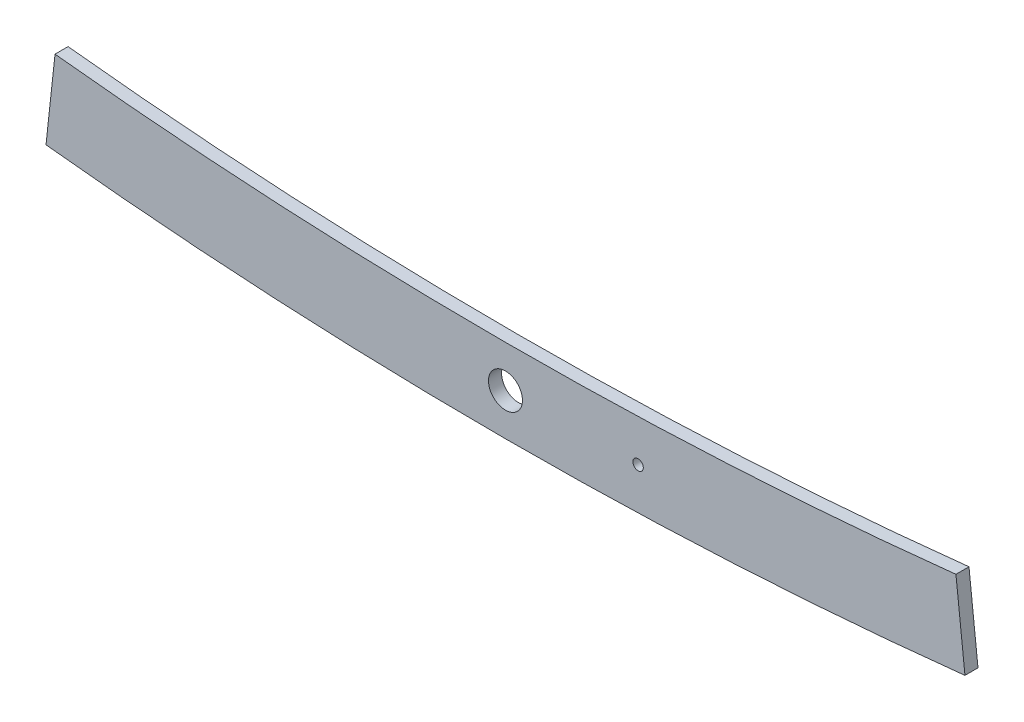
SolidWorks part; units mm, degrees
material "Plain Carbon Steel"
ref_plane "Front Plane" through (0, 0, 0) normal (0, 0, 1) x (1, 0, 0)
ref_plane "Top Plane" through (0, 0, 0) normal (0, 1, 0) x (1, 0, 0)
ref_plane "Right Plane" through (0, 0, 0) normal (1, 0, 0) x (0, 0, -1)
sketch "Sketch1" plane through (0, 0, 0) normal (0, 0, 1) x (1, 0, 0)
  line L0 (88, 4.759) -> (86.2745, 20.6657)
  line L1 (-88, 4.759) -> (-86.2745, 20.6657)
  arc A0 (-88, 4.759) -> (88, 4.759) centre (0, 816) ccw
  arc A1 (-86.2745, 20.6657) -> (86.2745, 20.6657) centre (0, 816) ccw
  dimension "D2" = 816
  dimension "D3" = 800
  dimension "D1" = 816
  dimension "D4" = 88
  dimension "D5" = 88
extrude "Boss-Extrude1" add sketch "Sketch1" along normal mid plane 2.5
sketch "Sketch2" plane through (0, 0, 0) normal (0, 0, 1) x (1, 0, 0)
  circle A0 centre (0, 8) radius 3.25
  dimension "D2" = 6.5
  dimension "D1" = 8
extrude "Cut-Extrude1" cut sketch "Sketch2" against normal mid plane 20
sketch "Sketch3" plane through (0, 0, 0) normal (0, 0, 1) x (1, 0, 0)
  circle A0 centre (25.4, 8.3994) radius 1
  dimension "D3" = 2
  dimension "D1" = 25.4
  dimension "D2" = 8.3994
extrude "Cut-Extrude2" cut sketch "Sketch3" against normal mid plane 20
